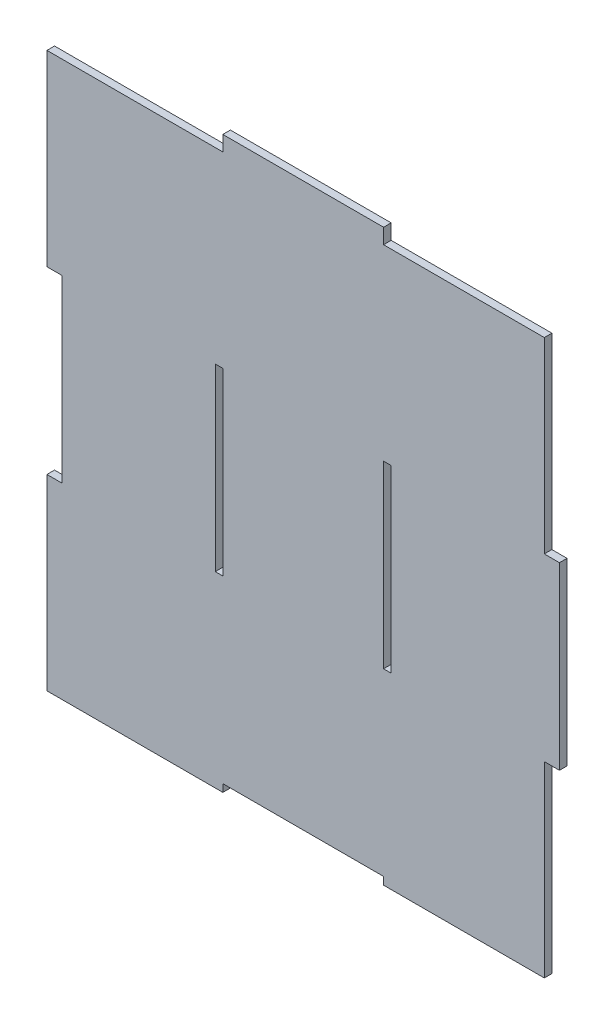
SolidWorks part; units mm, degrees
material "Delrin 2700 NC010, Low Viscosity Acetal Copolymer (SS)"
ref_plane "Front Plane" through (0, 0, 0) normal (0, 0, 1) x (1, 0, 0)
ref_plane "Top Plane" through (0, 0, 0) normal (0, 1, 0) x (1, 0, 0)
ref_plane "Right Plane" through (0, 0, 0) normal (1, 0, 0) x (0, 0, -1)
sketch "Sketch2" plane through (0, 0, 0) normal (0, 0, 1) x (1, 0, 0)
  line L0 (-113, 0) -> (-48.8417, 0)
  line L1 (-45.6667, 119.35) -> (-45.6667, 113)
  line L2 (-45.6667, 0) -> (21.6667, 0)
  line L3 (-45.6667, 119.35) -> (21.6667, 119.35)
  line L4 (95.35, 37.6667) -> (95.35, -37.6667)
  line L5 (-113, 37.6667) -> (-119.35, 37.6667)
  line L6 (-45.6667, 113) -> (21.6667, 113)
  line L7 (-12, 119.35) -> (-12, 113)
  line L8 (-113, 37.6667) -> (-113, -37.6667)
  line L9 (-113, 0) -> (-119.35, 0)
  line L10 (-45.6667, 116.175) -> (-116.175, 116.175)
  line L11 (-116.175, 116.175) -> (-116.175, 37.6667)
  line L12 (-116.175, 37.6667) -> (-113, 37.6667)
  line L13 (-113, 37.6667) -> (-113, -37.6667)
  line L14 (-48.8417, -37.6667) -> (-48.8417, 37.6667)
  line L15 (-48.8417, 37.6667) -> (-45.6667, 37.6667)
  line L16 (-45.6667, 37.6667) -> (-45.6667, -37.6667)
  line L17 (-119.35, 37.6667) -> (-119.35, -37.6667)
  line L18 (21.6667, 37.6667) -> (21.6667, -37.6667)
  line L19 (24.8417, 37.6667) -> (21.6667, 37.6667)
  line L20 (24.8417, -37.6667) -> (24.8417, 37.6667)
  line L21 (89, 37.6667) -> (89, -37.6667)
  line L22 (92.175, 37.6667) -> (89, 37.6667)
  line L23 (92.175, 116.175) -> (92.175, 37.6667)
  line L24 (-12, 119.35) -> (-12, -119.35)
  line L25 (21.6667, 116.175) -> (92.175, 116.175)
  line L26 (89, 0) -> (95.35, 0)
  line L27 (89, 37.6667) -> (89, -37.6667)
  line L28 (89, 37.6667) -> (95.35, 37.6667)
  line L29 (21.6667, 119.35) -> (21.6667, 113)
  line L30 (89, 0) -> (24.8417, 0)
  line L31 (21.6667, -119.35) -> (21.6667, -113)
  line L32 (89, -37.6667) -> (95.35, -37.6667)
  line L33 (21.6667, -116.175) -> (92.175, -116.175)
  line L34 (92.175, -116.175) -> (92.175, -37.6667)
  line L35 (92.175, -37.6667) -> (89, -37.6667)
  line L36 (24.8417, -37.6667) -> (21.6667, -37.6667)
  line L37 (-48.8417, -37.6667) -> (-45.6667, -37.6667)
  line L38 (-116.175, -37.6667) -> (-113, -37.6667)
  line L39 (-116.175, -116.175) -> (-116.175, -37.6667)
  line L40 (-45.6667, -116.175) -> (-116.175, -116.175)
  line L41 (-12, -119.35) -> (-12, -113)
  line L42 (-45.6667, -113) -> (21.6667, -113)
  line L43 (-113, -37.6667) -> (-119.35, -37.6667)
  line L44 (-45.6667, -119.35) -> (21.6667, -119.35)
  line L45 (-45.6667, -119.35) -> (-45.6667, -113)
  point P35 (-12, 0)
  point P36 (-12, 0)
  dimension "D1" = 3.175
  dimension "D2" = 37.6667
  dimension "D3" = 3.175
  dimension "D4" = 3.175
  dimension "D5" = 67.3333
  dimension "D6" = 67.3333
  dimension "D7" = 113
  dimension "D8" = 37.6667
  dimension "D9" = 101
  dimension "D10" = 3.175
  dimension "D11" = 3.175
  dimension "D13" = 0
  dimension "D14" = 0
extrude "Boss-Extrude1" add sketch "Sketch2" along normal blind 3.175 contours L24 L6 L1 L10 L11 L5 L8 L0 L14 L15 L16 L2 | L29 L3 L7 L6 | L30 L21 L22 L23 L25 L29 L6 L24 L2 L18 L19 L20 | L28 L22 L21 L26 L4 | L21 L32 L4 L26 | L24 L42 L31 L33 L34 L32 L21 L30 L20 L36 L18 L2 | L40 L45 L42 L24 L2 L16 L37 L14 L0 L8 L38 L39 | L6 L29 L3 L1 region at (-64.0656, 58.3724, 0) region at (-64.0656, -58.3724, 0) region at (40.0656, 58.3724, 0) region at (40.0656, -58.3724, 0) region at (4.8333, 116.175, 0) region at (92.175, -18.8333, 0) region at (92.175, 18.8333, 0)
sketch "Sketch3" plane through (0, 0, 3.175) normal (0, 0, 1) x (1, 0, 0)
  line L0 (-45.6667, -116.175) -> (-116.175, -116.175) construction
  line L1 (-116.175, 116.175) -> (-119.35, 116.175)
  line L2 (-116.175, 116.175) -> (-116.175, -116.175)
  line L3 (-116.175, -116.175) -> (-119.35, -116.175)
  line L4 (-119.35, 116.175) -> (-119.35, -116.175)
  line L5 (-116.175, -37.6667) -> (-113, -37.6667) construction
  line L6 (-113, 37.6667) -> (-119.35, 37.6667)
  line L7 (-113, 37.6667) -> (-113, -37.6667)
  line L8 (-113, -37.6667) -> (-119.35, -37.6667)
  line L9 (-119.35, 37.6667) -> (-119.35, -37.6667)
  line L10 (-45.6667, 119.35) -> (21.6667, 119.35) construction
  line L11 (21.6667, 116.175) -> (-45.6667, 116.175)
  line L12 (21.6667, 116.175) -> (21.6667, 122.525)
  line L13 (21.6667, 122.525) -> (-45.6667, 122.525)
  line L14 (-45.6667, 116.175) -> (-45.6667, 122.525)
  line L15 (-45.6667, 119.35) -> (-45.6667, 116.175) construction
  line M5 (21.6667, 119.35) -> (-45.6667, 119.35)
  line M8 (-116.175, 116.175) -> (-116.175, 37.6667)
  line M12 (-116.175, -37.6667) -> (-116.175, -116.175)
  dimension "D1" = 3.175
  dimension "D2" = 0
  dimension "D3" = 0
  dimension "D4" = 3.175
  dimension "D5" = 0
extrude "Boss-Extrude2" add sketch "Sketch3" against normal blind 3.175 contours L6 L1 L4 M8 | L8 L4 L3 M12 | L14 L12 L13 M5 region at (-117.7625, 76.9208, 3.175) region at (-117.7625, -76.9208, 3.175) region at (-12, 120.9375, 3.175)
sketch "Sketch4" plane through (0, 0, 3.175) normal (0, 0, 1) x (1, 0, 0)
  line L0 (21.6667, 116.175) -> (92.175, 116.175) construction
  line L1 (95.35, 37.6667) -> (89, 37.6667)
  line L2 (95.35, 37.6667) -> (95.35, 116.175)
  line L3 (95.35, 116.175) -> (89, 116.175)
  line L4 (89, 37.6667) -> (89, 116.175)
  line L5 (21.6667, -116.175) -> (92.175, -116.175) construction
  line L6 (89, 37.6667) -> (95.35, 37.6667)
  line L7 (89, 37.6667) -> (89, -37.6667)
  line L8 (89, -37.6667) -> (95.35, -37.6667)
  line L9 (95.35, 37.6667) -> (95.35, -37.6667)
  line L10 (95.35, -37.6667) -> (89, -37.6667)
  line L11 (95.35, -37.6667) -> (95.35, -116.175)
  line L12 (95.35, -116.175) -> (89, -116.175)
  line L13 (89, -37.6667) -> (89, -116.175)
  line L14 (92.175, 116.175) -> (92.175, 37.6667) construction
  line L16 (92.175, 116.175) -> (89, 116.175)
  line L17 (92.175, 116.175) -> (92.175, -116.175)
  line L18 (92.175, -116.175) -> (89, -116.175)
  line L19 (89, 116.175) -> (89, -116.175)
  line M13 (21.6667, -116.175) -> (92.175, -116.175)
  line M14 (92.175, -116.175) -> (92.175, -37.6667)
  line M18 (92.175, 37.6667) -> (92.175, 116.175)
  line M19 (92.175, 116.175) -> (21.6667, 116.175)
  dimension "D1" = 3.175
extrude "Cut-Extrude1" cut sketch "Sketch4" against normal blind 3.175 contours L4 L1 M18 M19 | L8 L13 M13 M14 region at (90.5875, 76.9208, 3.175) region at (90.5875, -76.9208, 3.175)
equation "\"D8@Sketch2\"=\"D2@Sketch2\""
equation "\"D11@Sketch2\"=\"D3@Sketch2\""
equation "\"D4@Sketch2\"=\"D3@Sketch2\""
equation "\"D10@Sketch2\"=\"D3@Sketch2\""
equation "\"Resolution Projector X\"= 1920"
equation "\"Resolution Projector Y\"= 1080"
equation "\"Resolution Build\"= 0.1"
equation "\"Size Build Volume X\"= \"Resolution Projector X\" * \"Resolution Build\""
equation "\"Size Build Volume Y\"= 2 * \"Resolution Projector Y\" * \"Resolution Build\""
equation "\"Size Build Volume Z\"= \"Size Build Volume Y\""
equation "\"Size Enclosure Internal X\"= 350mm"
equation "\"Size Enclosure Internal Y\"= \"Size Enclosure Internal X\""
equation "\"Size Enclosure Internal Z\"= \"Size Enclosure Internal X\""
equation "\"Size Enclosure External Z\"= 1000mm"
equation "\"Clearance Vat\"= 10mm'd_ clearance vat data"
equation "\"Size Vat X\"= \"Size Build Volume X\" + \"Clearance Vat\"'f_ size vat data"
equation "\"Size Vat Y\"= \"Size Build Volume Y\" + \"Clearance Vat\"'f_ size vat data"
equation "\"Size Vat Z\"= \"Size Build Volume Z\" + \"Clearance Vat\"'f_ size vat data"
equation "\"Thickness Vat\"= 3.175mm'g_ thickness vat data"
equation "\"width rib\"= 2 * \"Thickness Vat\"'g_ thickness of the Rib"
equation "\"width Lip on rib\"= \"Thickness Vat\" * 2'g_ thickness of the lip connected to the tab"
equation "\"height Lip on rib\"= \"width Lip on rib\"'g_ height of lip on rib structure"
equation "\"height adjustment\"= \"Thickness Vat\" * 2'g_ height adjustment for lip.  This flushes the top part of the tab to top of the walls"
equation "\"goofy tab x\"= \"Size Vat X\" * ( 1 / 3 ) - \"width rib\"'h_ goofy slot found on rib X"
equation "\"goofy tab y\"= \"Size Vat Y\" * ( 1 / 3 ) - \"width rib\"'h_ goofy slot found on rib Y"
equation "\"D9@Sketch2\"=\"Size Vat X\"/2mm"
equation "\"D5@Sketch2\"=\"D6@Sketch2\""
equation "\"D1@Sketch2\"=\"D10@Sketch2\""
equation "\"D2@Sketch2\"=\"D7@Sketch2\"/3"
equation "\"D6@Sketch2\"=\"Size Vat X\"/3"
equation "\"D3@Sketch2\"=\"Thickness Vat\""
equation "\"D7@Sketch2\"=\"Size Vat Z\"/2"
equation "\"D1@Boss-Extrude1\"=\"Thickness Vat\""
equation "\"D1@Sketch3\"=\"Thickness Vat\""
equation "\"D1@Boss-Extrude2\"=\"Thickness Vat\""
equation "\"D1@Sketch4\"=\"Thickness Vat\""
equation "\"D1@Cut-Extrude1\"=\"Thickness Vat\""
equation "\"D4@Sketch3\"=\"Thickness Vat\""
